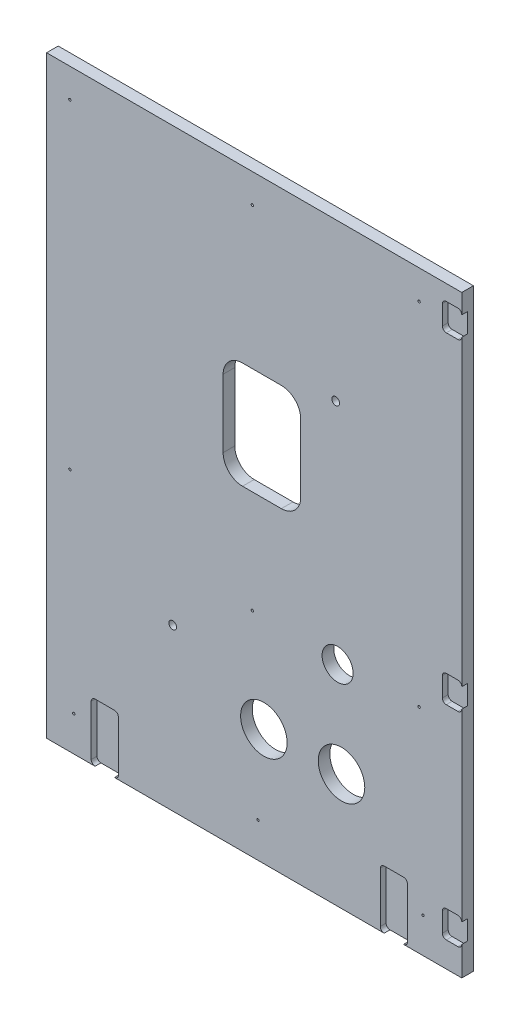
SolidWorks part; units mm, degrees
material "Фанера, берёза, ФСФ ВВ/С ГОСТ 3916.1-96"
ref_plane "Спереди" through (0, 0, 0) normal (0, 0, 1) x (1, 0, 0)
ref_plane "Сверху" through (0, 0, 0) normal (0, 1, 0) x (1, 0, 0)
ref_plane "Справа" through (0, 0, 0) normal (1, 0, 0) x (0, 0, -1)
sketch "Эскиз1" plane through (0, 0, 0) normal (0, 0, 1) x (1, 0, 0)
  line L1 (-535, -765) -> (535, -765)
  line L2 (-535, -765) -> (-535, 765)
  line L3 (-535, 765) -> (535, 765)
  line L4 (535, -765) -> (535, 765)
  line L5 (0, 765) -> (0, -765) construction
  line L6 (-535, 0) -> (535, 0) construction
  point P0 (0, 0)
  dimension "D1" = 1070
  dimension "D2" = 1530
extrude "Бобышка-Вытянуть1" add sketch "Эскиз1" along normal mid plane 30
sketch "Эскиз2" plane through (0, 0, 15) normal (0, 0, 1) x (1, 0, 0)
  line L0 (-535, 765) -> (-535, -765) construction
  line L1 (-30, 325) -> (70, 325)
  line L2 (-80, 275) -> (-80, 100)
  line L3 (-30, 50) -> (70, 50)
  line L4 (120, 275) -> (120, 100)
  line L5 (535, 765) -> (-535, 765) construction
  line L6 (535, -765) -> (535, 765) construction
  line L7 (-535, -765) -> (535, -765) construction
  arc A0 (70, 50) -> (120, 100) centre (70, 100) ccw
  arc A1 (-80, 100) -> (-30, 50) centre (-30, 100) ccw
  arc A2 (70, 325) -> (120, 275) centre (70, 275) cw
  arc A3 (-30, 325) -> (-80, 275) centre (-30, 275) ccw
  circle A4 centre (215, -225) radius 40
  circle A5 centre (225, -465) radius 60
  circle A6 centre (25, -465) radius 60
  circle A7 centre (210, 360) radius 10
  circle A8 centre (-210, -350) radius 10
  point P4 (20, 50)
  dimension "D5" = 50
  dimension "D6" = 80
  dimension "D9" = 120
  dimension "D13" = 20
  dimension "D1" = 275
  dimension "D2" = 200
  dimension "D3" = 455
  dimension "D4" = 440
  dimension "D7" = 320
  dimension "D8" = 540
  dimension "D10" = 310
  dimension "D11" = 300
  dimension "D12" = 510
  dimension "D14" = 405
  dimension "D15" = 325
  dimension "D16" = 325
  dimension "D17" = 415
extrude "Вырез-Вытянуть1" cut sketch "Эскиз2" against normal through all
sketch "Эскиз4" plane through (0, 0, 15) normal (0, 0, 1) x (1, 0, 0)
  line L0 (535, -765) -> (535, 765) construction
  line L1 (535, 765) -> (-535, 765) construction
  line L2 (-535, -765) -> (535, -765) construction
  line L3 (-535, 765) -> (-535, -765) construction
  line B0 (495, -105) -> (525, -105)
  line B1 (485, -115) -> (485, -165)
  line B2 (495, -175) -> (525, -175)
  line B3 (535, -115) -> (535, -165)
  arc B4 (525, -175) -> (535, -165) centre (525, -165) ccw
  arc B5 (485, -165) -> (495, -175) centre (495, -165) ccw
  arc B6 (525, -105) -> (535, -115) centre (525, -115) cw
  arc B7 (495, -105) -> (485, -115) centre (495, -115) ccw
  line B8 (495, -630) -> (525, -630)
  line B9 (485, -640) -> (485, -690)
  line B10 (495, -700) -> (525, -700)
  line B11 (535, -640) -> (535, -690)
  arc B12 (525, -700) -> (535, -690) centre (525, -690) ccw
  arc B13 (485, -690) -> (495, -700) centre (495, -690) ccw
  arc B14 (525, -630) -> (535, -640) centre (525, -640) cw
  arc B15 (495, -630) -> (485, -640) centre (495, -640) ccw
  line B16 (-385, -615) -> (-385, -765) construction
  line B17 (-410, -615) -> (-360, -615)
  line B18 (-420, -625) -> (-420, -755)
  line B19 (-410, -765) -> (-360, -765)
  line B20 (-350, -625) -> (-350, -755)
  arc B21 (-360, -765) -> (-350, -755) centre (-360, -755) ccw
  arc B22 (-420, -755) -> (-410, -765) centre (-410, -755) ccw
  arc B23 (-360, -615) -> (-350, -625) centre (-360, -625) cw
  arc B24 (-410, -615) -> (-420, -625) centre (-410, -625) ccw
  line B25 (495, 725) -> (525, 725)
  line B26 (485, 715) -> (485, 665)
  line B27 (495, 655) -> (525, 655)
  line B28 (535, 715) -> (535, 665)
  arc B29 (525, 655) -> (535, 665) centre (525, 665) ccw
  arc B30 (485, 665) -> (495, 655) centre (495, 665) ccw
  arc B31 (525, 725) -> (535, 715) centre (525, 715) cw
  arc B32 (495, 725) -> (485, 715) centre (495, 715) ccw
  line B33 (335, -615) -> (385, -615)
  line B34 (325, -625) -> (325, -755)
  line B35 (335, -765) -> (385, -765)
  line B36 (395, -625) -> (395, -755)
  arc B37 (385, -765) -> (395, -755) centre (385, -755) ccw
  arc B38 (325, -755) -> (335, -765) centre (335, -755) ccw
  arc B39 (385, -615) -> (395, -625) centre (385, -625) cw
  arc B40 (335, -615) -> (325, -625) centre (335, -625) ccw
  dimension "D1" = 40
  dimension "D2" = 870
  dimension "D3" = 65
  dimension "D4" = 115
  dimension "D5" = 140
sketch_block_instance "Блок1-2"
sketch_block "Блок1" parameters "D3"=10, "D1"=70, "D2"=50
sketch_block_instance "Блок1-3"
sketch_block "Блок1" parameters "D3"=10, "D1"=70, "D2"=50
sketch_block_instance "Блок3-1"
sketch_block "Блок3" parameters "D2"=10, "D1"=70, "D3"=50
sketch_block_instance "Блок1-1"
sketch_block "Блок1" parameters "D3"=10, "D1"=70, "D2"=50
sketch_block_instance "Блок3-2"
extrude "Вырез-Вытянуть2" cut sketch "Эскиз4" against normal blind 15
sketch "Эскиз5" plane through (0, 0, 15) normal (0, 0, 1) x (1, 0, 0)
  line L0 (535, 765) -> (-535, 765) construction
  line L1 (-535, 765) -> (-535, -765) construction
  line L2 (-535, -765) -> (-410, -765) construction
  line L3 (-360, -765) -> (335, -765) construction
  line L4 (385, -765) -> (535, -765) construction
  line L5 (535, -765) -> (535, -690) construction
  circle B0 centre (-475, 690) radius 3
  circle B1 centre (-5, 690) radius 3
  circle B2 centre (425, 690) radius 3
  circle B3 centre (-475, -135) radius 3
  circle B4 centre (-5, -215) radius 3
  circle B5 centre (425, -215) radius 3
  circle B6 centre (-465, -675) radius 3
  circle B7 centre (10, -675) radius 3
  circle B8 centre (435, -675) radius 3
  dimension "D1" = 75
  dimension "D2" = 60
  dimension "D3" = 470
  dimension "D4" = 430
  dimension "D5" = 825
  dimension "D6" = 905
  dimension "D7" = 70
  dimension "D8" = 90
  dimension "D9" = 90
  dimension "D10" = 545
  dimension "D11" = 90
  dimension "D12" = 100
sketch_block_instance "Блок4-1"
sketch_block "Блок4" parameters "D1"=6
sketch_block_instance "Блок4-2"
sketch_block_instance "Блок4-3"
sketch_block_instance "Блок4-4"
sketch_block_instance "Блок4-5"
sketch_block_instance "Блок4-6"
sketch_block_instance "Блок4-7"
sketch_block_instance "Блок4-8"
sketch_block_instance "Блок4-9"
extrude "Вырез-Вытянуть3" cut sketch "Эскиз5" against normal through all
equation "\"ширина 1-я панель\"=1145"
equation "\"длина панелей\"=1530"
equation "\"толщина дсп\"=30"
equation "\"ширина 2-я панель\"=1070"
equation "\"D2@Эскиз1\"=\"длина панелей\""
equation "\"D1@Эскиз1\"=\"ширина 2-я панель\""
